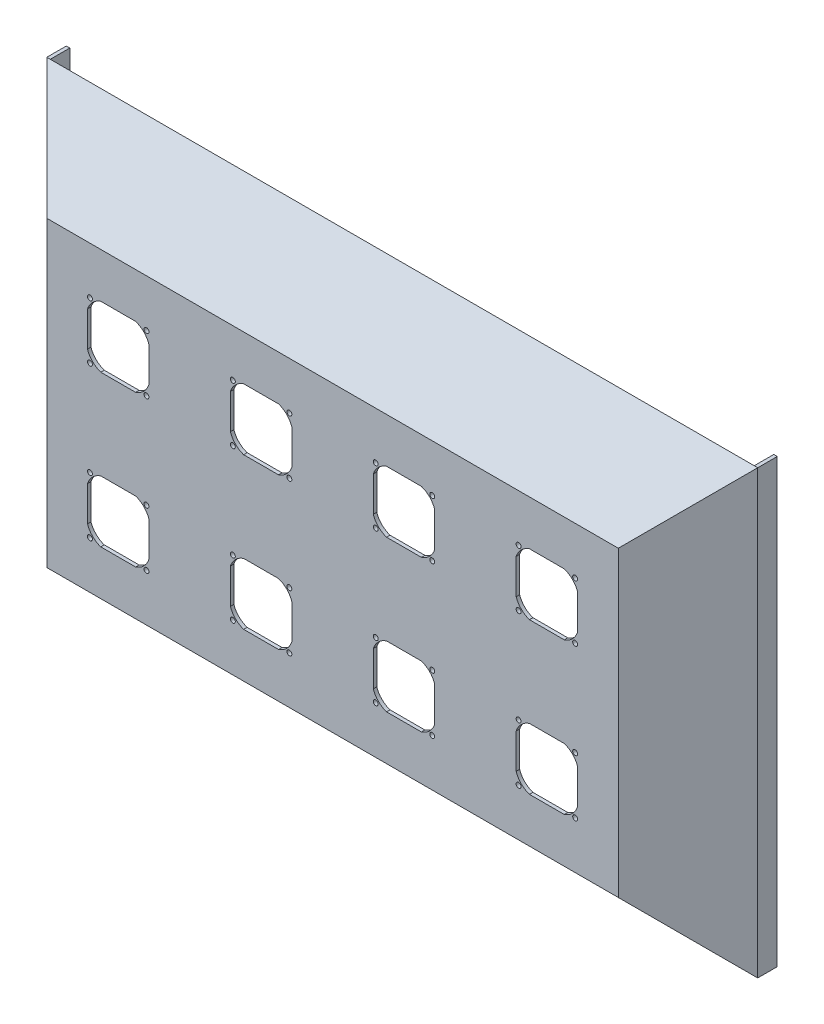
SolidWorks part; units mm, degrees
material "Custom Plastic"
ref_plane "X-Y Datum" through (0, 0, 0) normal (0, 0, 1) x (1, 0, 0)
ref_plane "X-Z Datum" through (0, 0, 0) normal (0, 1, 0) x (1, 0, 0)
ref_plane "Y-Z Datum" through (0, 0, 0) normal (1, 0, 0) x (0, 0, -1)
sketch "Sketch1" plane through (0, 0, 0) normal (0, 0, 1) x (1, 0, 0)
  line L1 (-323.85, 201.295) -> (323.85, 201.295)
  line L2 (-323.85, 201.295) -> (-323.85, -201.295)
  line L3 (-323.85, -201.295) -> (323.85, -201.295)
  line L4 (323.85, 201.295) -> (323.85, -201.295)
  line L5 (-323.85, 201.295) -> (323.85, -201.295) construction
  line L6 (-323.85, -201.295) -> (323.85, 201.295) construction
  point P0 (0, 0)
  dimension "D1" = 647.7
  dimension "D2" = 402.59
extrude "Boss-Extrude1" add sketch "Sketch1" along normal blind 63.5 contours L1 L4 L3 L2
chamfer "Chamfer1" distance 63.5 angle 45 2 edges at (0, 201.295, 63.5) (0, -201.295, 63.5)
chamfer "Chamfer2" distance 63.5 angle 45 2 edges at (-323.85, 0, 63.5) (323.85, 0, 63.5)
sketch "Sketch3" plane through (0, 0, 0) normal (0, 0, 1) x (1, 0, 0)
  line L1 (-323.85, 201.295) -> (323.85, 201.295)
  line L2 (-323.85, 201.295) -> (-323.85, -201.295)
  line L3 (-323.85, -201.295) -> (323.85, -201.295)
  line L4 (323.85, 201.295) -> (323.85, -201.295)
sketch "Sketch2" plane through (0, 0, 63.5) normal (0, 0, 1) x (1, 0, 0)
  line L0 (0, 137.795) -> (0, 0) construction
  line L1 (-224.5125, 98.1475) -> (-166.0125, 98.1475) construction
  line L2 (-224.5125, 98.1475) -> (-224.5125, 39.6475) construction
  line L3 (-224.5125, 39.6475) -> (-166.0125, 39.6475) construction
  line L4 (-166.0125, 98.1475) -> (-166.0125, 39.6475) construction
  line L5 (-224.5125, 98.1475) -> (-166.0125, 39.6475) construction
  line L6 (-224.5125, 39.6475) -> (-166.0125, 98.1475) construction
  line L7 (-35.8375, 98.1475) -> (-35.8375, 39.6475)
  line L8 (-35.8375, 39.6475) -> (-94.3375, 39.6475)
  line L9 (260.35, 137.795) -> (-260.35, 137.795) construction
  line L10 (-94.3375, 98.1475) -> (-94.3375, 39.6475)
  line L11 (0, 0) -> (0, -137.795) construction
  line L12 (-260.35, -137.795) -> (260.35, -137.795) construction
  line L13 (0, 0) -> (-260.35, 0) construction
  line L14 (-260.35, 137.795) -> (-260.35, -137.795) construction
  line L15 (0, 0) -> (260.35, 0) construction
  line L16 (260.35, -137.795) -> (260.35, 137.795) construction
  line L17 (-130.175, 0) -> (-130.175, 137.795) construction
  line L18 (0, 68.8975) -> (-130.175, 68.8975) construction
  line L19 (-130.175, 68.8975) -> (-260.35, 68.8975) construction
  line L20 (-35.8375, 98.1475) -> (-94.3375, 98.1475)
  line L21 (35.8375, 98.1475) -> (94.3375, 98.1475)
  line L22 (35.8375, 98.1475) -> (35.8375, 39.6475)
  line L23 (35.8375, 39.6475) -> (94.3375, 39.6475)
  line L24 (94.3375, 98.1475) -> (94.3375, 39.6475)
  line L25 (224.5125, 98.1475) -> (224.5125, 39.6475)
  line L26 (224.5125, 39.6475) -> (166.0125, 39.6475)
  line L27 (166.0125, 98.1475) -> (166.0125, 39.6475)
  line L28 (224.5125, 98.1475) -> (166.0125, 98.1475)
  line L29 (224.5125, -98.1475) -> (224.5125, -39.6475)
  line L30 (224.5125, -39.6475) -> (166.0125, -39.6475)
  line L31 (166.0125, -98.1475) -> (166.0125, -39.6475)
  line L32 (224.5125, -98.1475) -> (166.0125, -98.1475)
  line L33 (94.3375, -98.1475) -> (94.3375, -39.6475)
  line L34 (35.8375, -39.6475) -> (94.3375, -39.6475)
  line L35 (35.8375, -98.1475) -> (35.8375, -39.6475)
  line L36 (35.8375, -98.1475) -> (94.3375, -98.1475)
  line L37 (-35.8375, -98.1475) -> (-35.8375, -39.6475)
  line L38 (-35.8375, -98.1475) -> (-94.3375, -98.1475)
  line L39 (-94.3375, -98.1475) -> (-94.3375, -39.6475)
  line L40 (-35.8375, -39.6475) -> (-94.3375, -39.6475)
  line L41 (-224.5125, -39.6475) -> (-166.0125, -39.6475)
  line L42 (-166.0125, -98.1475) -> (-166.0125, -39.6475)
  line L43 (-224.5125, -98.1475) -> (-166.0125, -98.1475)
  line L44 (-224.5125, -98.1475) -> (-224.5125, -39.6475)
  line L45 (-211.1375, 96.8775) -> (-179.3875, 96.8775)
  line L46 (-221.0125, 94.6475) -> (-169.5125, 94.6475) construction
  line L47 (-221.0125, 94.6475) -> (-221.0125, 43.1475) construction
  line L48 (-221.0125, 43.1475) -> (-169.5125, 43.1475) construction
  line L49 (-169.5125, 94.6475) -> (-169.5125, 43.1475) construction
  line L50 (-221.0125, 94.6475) -> (-169.5125, 43.1475) construction
  line L51 (-221.0125, 43.1475) -> (-169.5125, 94.6475) construction
  line L52 (-211.1375, 40.9175) -> (-179.3875, 40.9175)
  line L53 (-223.2425, 53.0225) -> (-223.2425, 84.7725)
  line L54 (-195.2625, 68.8975) -> (-195.2625, 43.1475) construction
  line L55 (-167.2825, 53.0225) -> (-167.2825, 84.7725)
  line L56 (-37.1075, 53.0225) -> (-37.1075, 84.7725)
  line L57 (-49.2125, 40.9175) -> (-80.9625, 40.9175)
  line L58 (-93.0675, 53.0225) -> (-93.0675, 84.7725)
  line L59 (-49.2125, 96.8775) -> (-80.9625, 96.8775)
  line L60 (37.1075, 53.0225) -> (37.1075, 84.7725)
  line L61 (49.2125, 40.9175) -> (80.9625, 40.9175)
  line L62 (93.0675, 53.0225) -> (93.0675, 84.7725)
  line L63 (49.2125, 96.8775) -> (80.9625, 96.8775)
  line L64 (211.1375, 40.9175) -> (179.3875, 40.9175)
  line L65 (223.2425, 53.0225) -> (223.2425, 84.7725)
  line L66 (167.2825, 53.0225) -> (167.2825, 84.7725)
  line L67 (211.1375, 96.8775) -> (179.3875, 96.8775)
  line L68 (223.2425, -53.0225) -> (223.2425, -84.7725)
  line L69 (211.1375, -40.9175) -> (179.3875, -40.9175)
  line L70 (167.2825, -53.0225) -> (167.2825, -84.7725)
  line L71 (211.1375, -96.8775) -> (179.3875, -96.8775)
  line L72 (37.1075, -53.0225) -> (37.1075, -84.7725)
  line L73 (49.2125, -40.9175) -> (80.9625, -40.9175)
  line L74 (93.0675, -53.0225) -> (93.0675, -84.7725)
  line L75 (49.2125, -96.8775) -> (80.9625, -96.8775)
  line L76 (-93.0675, -53.0225) -> (-93.0675, -84.7725)
  line L77 (-49.2125, -40.9175) -> (-80.9625, -40.9175)
  line L78 (-37.1075, -53.0225) -> (-37.1075, -84.7725)
  line L79 (-49.2125, -96.8775) -> (-80.9625, -96.8775)
  line L80 (-223.2425, -53.0225) -> (-223.2425, -84.7725)
  line L81 (-211.1375, -40.9175) -> (-179.3875, -40.9175)
  line L82 (-167.2825, -53.0225) -> (-167.2825, -84.7725)
  line L83 (-211.1375, -96.8775) -> (-179.3875, -96.8775)
  circle A0 centre (-221.0125, 94.6475) radius 2.25
  circle A1 centre (-169.5125, 94.6475) radius 2.25
  circle A2 centre (-221.0125, 43.1475) radius 2.25
  circle A3 centre (-169.5125, 43.1475) radius 2.25
  circle A4 centre (-39.3375, 43.1475) radius 2.25
  circle A5 centre (-90.8375, 94.6475) radius 2.25
  circle A6 centre (-39.3375, 94.6475) radius 2.25
  circle A7 centre (-90.8375, 43.1475) radius 2.25
  circle A8 centre (39.3375, 94.6475) radius 2.25
  circle A9 centre (39.3375, 43.1475) radius 2.25
  circle A10 centre (90.8375, 43.1475) radius 2.25
  circle A11 centre (90.8375, 94.6475) radius 2.25
  circle A12 centre (169.5125, 94.6475) radius 2.25
  circle A13 centre (169.5125, 43.1475) radius 2.25
  circle A14 centre (221.0125, 43.1475) radius 2.25
  circle A15 centre (221.0125, 94.6475) radius 2.25
  circle A16 centre (221.0125, -43.1475) radius 2.25
  circle A17 centre (221.0125, -94.6475) radius 2.25
  circle A18 centre (169.5125, -43.1475) radius 2.25
  circle A19 centre (169.5125, -94.6475) radius 2.25
  circle A20 centre (90.8375, -43.1475) radius 2.25
  circle A21 centre (90.8375, -94.6475) radius 2.25
  circle A22 centre (39.3375, -43.1475) radius 2.25
  circle A23 centre (39.3375, -94.6475) radius 2.25
  circle A24 centre (-39.3375, -94.6475) radius 2.25
  circle A25 centre (-39.3375, -43.1475) radius 2.25
  circle A26 centre (-90.8375, -43.1475) radius 2.25
  circle A27 centre (-90.8375, -94.6475) radius 2.25
  circle A28 centre (-169.5125, -43.1475) radius 2.25
  circle A29 centre (-221.0125, -43.1475) radius 2.25
  circle A30 centre (-169.5125, -94.6475) radius 2.25
  circle A31 centre (-221.0125, -94.6475) radius 2.25
  arc A32 (-223.2425, 84.7725) -> (-211.1375, 96.8775) centre (-205.1559, 78.7909) cw
  arc A33 (-179.3875, 96.8775) -> (-167.2825, 84.7725) centre (-185.3691, 78.7909) cw
  arc A34 (-223.2425, 53.0225) -> (-211.1375, 40.9175) centre (-205.1559, 59.0041) ccw
  arc A35 (-179.3875, 40.9175) -> (-167.2825, 53.0225) centre (-185.3691, 59.0041) ccw
  arc A36 (-37.1075, 53.0225) -> (-49.2125, 40.9175) centre (-55.1941, 59.0041) cw
  arc A37 (-80.9625, 40.9175) -> (-93.0675, 53.0225) centre (-74.9809, 59.0041) cw
  arc A38 (-80.9625, 96.8775) -> (-93.0675, 84.7725) centre (-74.9809, 78.7909) ccw
  arc A39 (-37.1075, 84.7725) -> (-49.2125, 96.8775) centre (-55.1941, 78.7909) ccw
  arc A40 (37.1075, 84.7725) -> (49.2125, 96.8775) centre (55.1941, 78.7909) cw
  arc A41 (37.1075, 53.0225) -> (49.2125, 40.9175) centre (55.1941, 59.0041) ccw
  arc A42 (80.9625, 40.9175) -> (93.0675, 53.0225) centre (74.9809, 59.0041) ccw
  arc A43 (80.9625, 96.8775) -> (93.0675, 84.7725) centre (74.9809, 78.7909) cw
  arc A44 (179.3875, 40.9175) -> (167.2825, 53.0225) centre (185.3691, 59.0041) cw
  arc A45 (223.2425, 53.0225) -> (211.1375, 40.9175) centre (205.1559, 59.0041) cw
  arc A46 (179.3875, 96.8775) -> (167.2825, 84.7725) centre (185.3691, 78.7909) ccw
  arc A47 (223.2425, 84.7725) -> (211.1375, 96.8775) centre (205.1559, 78.7909) ccw
  arc A48 (223.2425, -84.7725) -> (211.1375, -96.8775) centre (205.1559, -78.7909) cw
  arc A49 (223.2425, -53.0225) -> (211.1375, -40.9175) centre (205.1559, -59.0041) ccw
  arc A50 (179.3875, -40.9175) -> (167.2825, -53.0225) centre (185.3691, -59.0041) ccw
  arc A51 (179.3875, -96.8775) -> (167.2825, -84.7725) centre (185.3691, -78.7909) cw
  arc A52 (37.1075, -53.0225) -> (49.2125, -40.9175) centre (55.1941, -59.0041) cw
  arc A53 (80.9625, -40.9175) -> (93.0675, -53.0225) centre (74.9809, -59.0041) cw
  arc A54 (80.9625, -96.8775) -> (93.0675, -84.7725) centre (74.9809, -78.7909) ccw
  arc A55 (37.1075, -84.7725) -> (49.2125, -96.8775) centre (55.1941, -78.7909) ccw
  arc A56 (-80.9625, -40.9175) -> (-93.0675, -53.0225) centre (-74.9809, -59.0041) ccw
  arc A57 (-37.1075, -53.0225) -> (-49.2125, -40.9175) centre (-55.1941, -59.0041) ccw
  arc A58 (-37.1075, -84.7725) -> (-49.2125, -96.8775) centre (-55.1941, -78.7909) cw
  arc A59 (-80.9625, -96.8775) -> (-93.0675, -84.7725) centre (-74.9809, -78.7909) cw
  arc A60 (-223.2425, -53.0225) -> (-211.1375, -40.9175) centre (-205.1559, -59.0041) cw
  arc A61 (-179.3875, -40.9175) -> (-167.2825, -53.0225) centre (-185.3691, -59.0041) cw
  arc A62 (-179.3875, -96.8775) -> (-167.2825, -84.7725) centre (-185.3691, -78.7909) ccw
  arc A63 (-223.2425, -84.7725) -> (-211.1375, -96.8775) centre (-205.1559, -78.7909) ccw
  point P0 (-195.2625, 68.8975)
  point P9 (0, 0)
  point P17 (0, 0)
  point P26 (-195.2625, 68.8975)
  point P55 (-195.2625, 68.8975)
  point P123 (-195.2625, 96.8775)
  point P124 (-195.2625, 94.6475)
  point P130 (-223.2425, 68.8975)
  point P221 (0, 0)
  dimension "D4" = 31.75
  dimension "D1" = 58.5
  dimension "D2" = 58.5
  dimension "D3" = 51.5
  dimension "D5" = 1.27
  dimension "D6" = 31.75
  dimension "D7" = 1.27
extrude "Boss-Extrude2" add sketch "Sketch3" against normal blind 17.78
shell "Shell1" thickness 3.175 removed face at (0, 0, -17.78)
sketch "Sketch4" plane through (0, 0, -17.78) normal (0, 0, -1) x (-1, 0, 0)
  line L1 (-320.675, 201.295) -> (320.675, 201.295)
  line L3 (-320.675, 198.12) -> (320.675, 198.12)
  line L8 (-320.675, 198.12) -> (-320.675, 201.295)
  line L9 (320.675, 201.295) -> (320.675, 198.12)
extrude "Cut-Extrude1" cut sketch "Sketch4" against normal blind 17.78
extrude "Cut-Extrude3" cut sketch "Sketch2" against normal through all both contours L56 A39 L59 A38 L58 A37 L57 A36 | A2 | A3 | A6 | A7 | A4 | A43 L63 A40 L60 A41 L61 A42 L62 | L65 A47 L67 A46 L66 A44 L64 A45 | L80 A63 L83 A62 L82 A61 L81 A60 | A59 L79 A58 L78 A57 L77 A56 L76 | L72 A55 L75 A54 L74 A53 L73 A52 | A51 L71 A48 L68 A49 L69 A50 L70 | A8 | A11 | A10 | A29 | A28 | A30 | A26 | A25 | A27 | A22 | A23 | A20 | A21 | A18 | A16 | A19 | A17 | A32 L45 A33 L55 A35 L52 A34 L53 | A0 | A1 | A5 | A9 | A12 | A13 | A15 | A14 | A31 | A24 region at (-65.0875, 68.8975, 63.5) region at (65.0875, 68.8975, 63.5) region at (195.2625, 68.8975, 63.5) region at (195.2625, -68.8975, 63.5) region at (65.0875, -68.8975, 63.5) region at (-65.0875, -68.8975, 63.5) region at (-195.2625, -68.8975, 63.5) region at (-221.0125, 43.1475, 63.5) region at (-169.5125, 43.1475, 63.5) region at (-39.3375, 43.1475, 63.5) region at (-39.3375, 94.6475, 63.5) region at (-90.8375, 43.1475, 63.5) region at (39.3375, 94.6475, 63.5) region at (90.8375, 43.1475, 63.5) region at (90.8375, 94.6475, 63.5) region at (221.0125, -43.1475, 63.5) region at (221.0125, -94.6475, 63.5) region at (169.5125, -43.1475, 63.5) region at (169.5125, -94.6475, 63.5) region at (90.8375, -43.1475, 63.5) region at (90.8375, -94.6475, 63.5) region at (39.3375, -43.1475, 63.5) region at (39.3375, -94.6475, 63.5) region at (-39.3375, -43.1475, 63.5) region at (-90.8375, -43.1475, 63.5) region at (-90.8375, -94.6475, 63.5) region at (-169.5125, -43.1475, 63.5) region at (-221.0125, -43.1475, 63.5) region at (-169.5125, -94.6475, 63.5)
